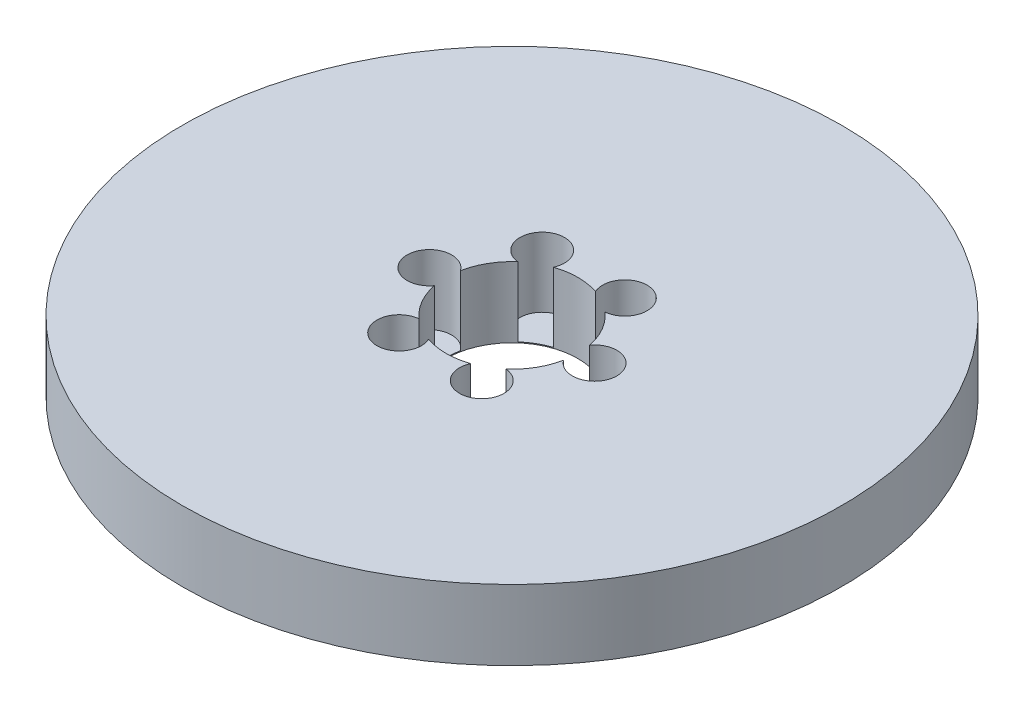
SolidWorks part; units mm, degrees
ref_plane "Front Plane" through (0, 0, 0) normal (0, 0, 1) x (1, 0, 0)
ref_plane "Top Plane" through (0, 0, 0) normal (0, 1, 0) x (1, 0, 0)
ref_plane "Right Plane" through (0, 0, 0) normal (1, 0, 0) x (0, 0, -1)
sketch "Sketch1" plane through (0, 0, 0) normal (0, 1, 0) x (1, 0, 0)
  circle A0 centre (0, 0) radius 37.5
  dimension "FLANGE_OD" = 75
extrude "Boss-Extrude1" add sketch "Sketch1" along normal blind 8
sketch "Sketch2" plane through (0, 0, 0) normal (0, 1, 0) x (1, 0, 0)
  circle A0 centre (0, 0) radius 7.5
  dimension "BORE_D" = 15
extrude "Cut-Extrude1" cut sketch "Sketch2" along normal through all
sketch "Sketch3" plane through (0, 8, 0) normal (0, 1, 0) x (1, 0, 0)
  circle A0 centre (0, 0) radius 9.3993 construction
  circle A1 centre (-9.3993, 0) radius 2.5323
  dimension "BOLT_D" = 5.0646
  dimension "BOLT_PCD" = 18.7987
extrude "Cut-Extrude2" cut sketch "Sketch3" against normal blind 7.897
pattern_circular "CirPattern1" count 6 over 360 about axis through (0, 0, 0) along (0, 1, 0) of "Cut-Extrude2"
